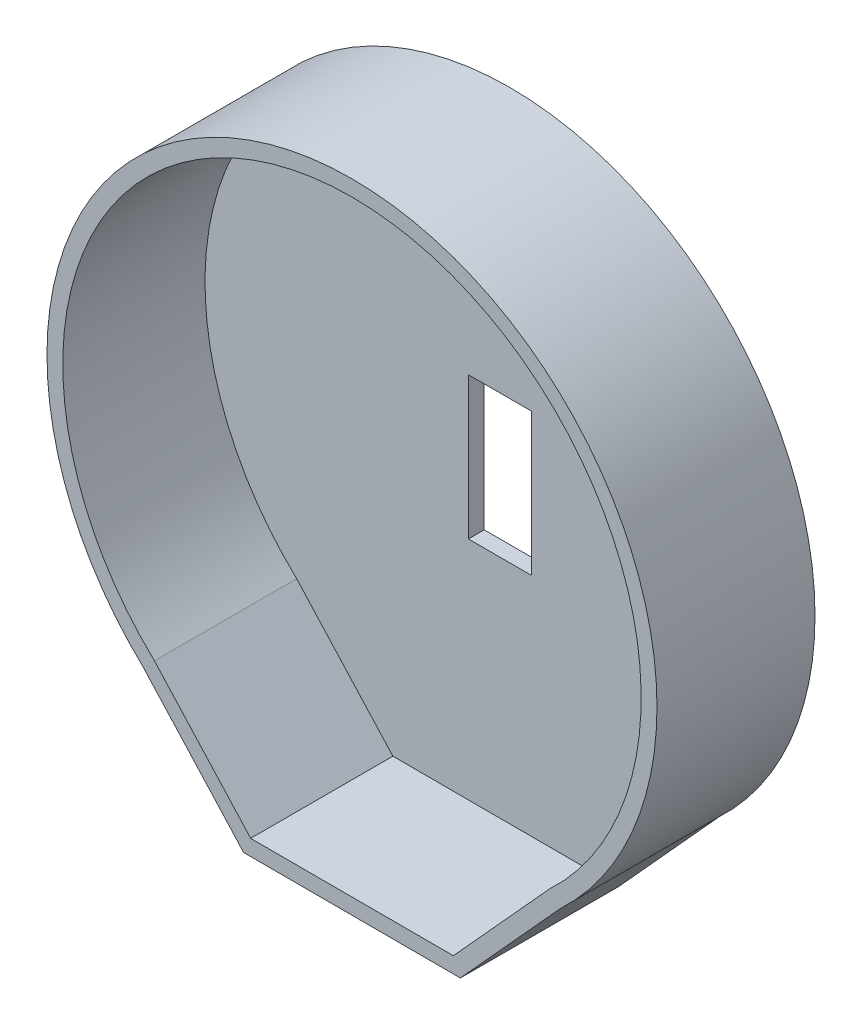
SolidWorks part; units mm, degrees
ref_plane "Front Plane" through (0, 0, 0) normal (0, 0, 1) x (1, 0, 0)
ref_plane "Top Plane" through (0, 0, 0) normal (0, 1, 0) x (1, 0, 0)
ref_plane "Right Plane" through (0, 0, 0) normal (1, 0, 0) x (0, 0, -1)
sketch "Sketch1" plane through (0, 0, 0) normal (0, 0, 1) x (1, 0, 0)
  line L20 (-17.3105, -21.8239) -> (-3.5977, -21.8436)
  line L21 (-3.5977, -21.8436) -> (2.7579, -14.8425)
  line L22 (-17.3105, -21.8239) -> (-23.6681, -14.8425)
  arc A4 (2.7579, -14.8425) -> (-23.6681, -14.8425) centre (-10.4551, -0.7746) ccw
  dimension "D1" = 19.3
extrude "Boss-Extrude1" add sketch "Sketch1" along normal blind 10 contours A4 L22 L20 L21
shell "Shell1" thickness 1 removed face at (-10.4546, -9.9961, 10)
sketch "Sketch2" plane through (0, 0, 10) normal (0, 0, 1) x (1, 0, 0)
  line L3 (-12.0905, 2.4705) -> (-8.0905, 2.4705)
  line L4 (-12.0905, 2.4705) -> (-12.0905, -6.5295)
  line L5 (-12.0905, -6.5295) -> (-8.0905, -6.5295)
  line L6 (-8.0905, 2.4705) -> (-8.0905, -6.5295)
  line L7 (-12.0905, 2.4705) -> (-8.0905, -6.5295) construction
  line L8 (-12.0905, -6.5295) -> (-8.0905, 2.4705) construction
  point P8 (-10.0905, -2.0295)
  dimension "D1" = 9
  dimension "D2" = 4
extrude "Cut-Extrude1" cut sketch "Sketch2" against normal up to next
